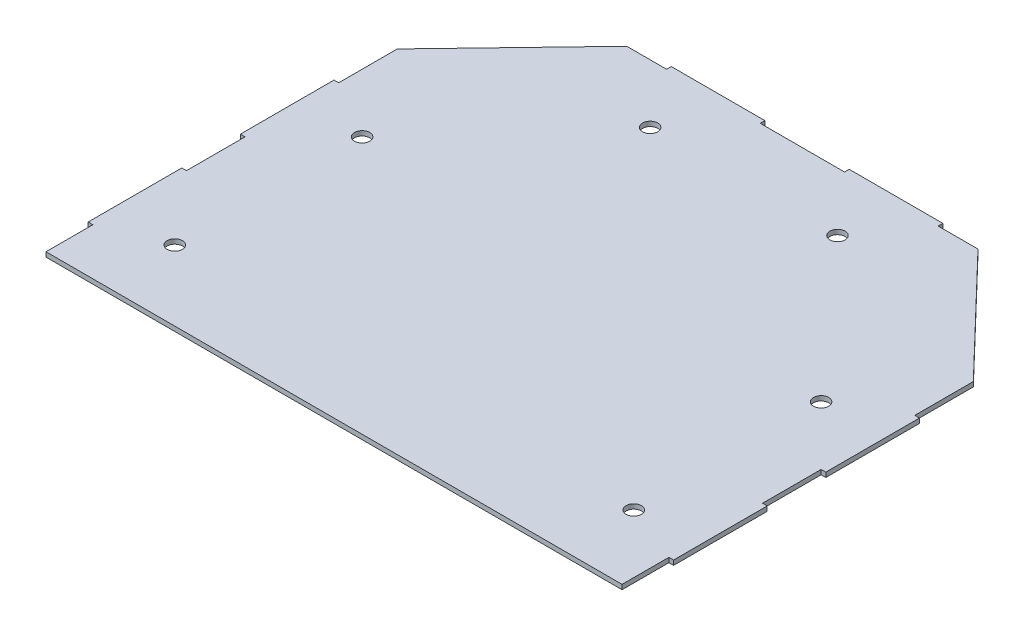
SolidWorks part; units mm, degrees
material "ABS PC"
ref_plane "Спереди" through (0, 0, 0) normal (0, 0, 1) x (1, 0, 0)
ref_plane "Сверху" through (0, 0, 0) normal (0, 1, 0) x (1, 0, 0)
ref_plane "Справа" through (0, 0, 0) normal (1, 0, 0) x (0, 0, -1)
sketch "Sketch1" plane through (0, 0, 0) normal (0, 1, 0) x (1, 0, 0)
  line L0 (-123, 0) -> (-123, 20)
  line L1 (-123, 150) -> (-75, 200)
  line L2 (-75, 200) -> (-58, 200)
  line L3 (0, 200) -> (0, 0) construction
  line L4 (123, 0) -> (-123, 0)
  line L5 (-123, 0) -> (-123.0387, -0.1129)
  line L6 (-123, 20) -> (-125, 20)
  line L7 (-125, 20) -> (-125, 60)
  line L8 (-125, 60) -> (-123, 60)
  line L9 (-123, 85) -> (-125, 85)
  line L10 (-125, 85) -> (-125, 125)
  line L11 (-125, 125) -> (-123, 125)
  line L12 (-123, 125) -> (-123, 150)
  line L13 (-123, 60) -> (-123, 85)
  line L14 (-58, 200) -> (-58, 202)
  line L15 (-58, 202) -> (-18, 202)
  line L16 (-18, 202) -> (-18, 200)
  line L17 (-18, 200) -> (18, 200)
  line L18 (18, 202) -> (18, 200)
  line L19 (58, 202) -> (18, 202)
  line L20 (58, 200) -> (58, 202)
  line L21 (123, 60) -> (123, 85)
  line L22 (123, 125) -> (123, 150)
  line L23 (125, 125) -> (123, 125)
  line L24 (125, 85) -> (125, 125)
  line L25 (123, 85) -> (125, 85)
  line L26 (125, 60) -> (123, 60)
  line L27 (125, 20) -> (125, 60)
  line L28 (123, 20) -> (125, 20)
  line L29 (123, 0) -> (123.0387, -0.1129)
  line L30 (75, 200) -> (58, 200)
  line L31 (123, 150) -> (75, 200)
  line L32 (123, 0) -> (123, 20)
  dimension "D1" = 123
  dimension "D2" = 200
  dimension "D3" = 50
  dimension "D4" = 75
  dimension "D5" = 40
  dimension "D6" = 180
  dimension "D7" = 115
  dimension "D8" = 2
  dimension "D9" = 65
extrude "Boss-Extrude1" add sketch "Sketch1" along normal blind 2 contours L3 L17 L16 L15 L14 L2 L1 L12 L11 L10 L9 L13 L8 L7 L6 L0 L4 | L17 L3 L4 L32 L28 L27 L26 L21 L25 L24 L23 L22 L31 L30 L20 L19 L18 region at (-59.5338, 0, -95.9255) region at (59.5338, 0, -95.9255)
sketch "Sketch2" plane through (0, 2, 0) normal (0, 1, 0) x (-1, 0, 0)
  line L0 (98, -110) -> (98, -30) construction
  line L1 (-98, -110) -> (-98, -30) construction
  line L2 (98, -110) -> (0, -110) construction
  line L3 (0, -110) -> (-98, -110) construction
  line L4 (-123, 0) -> (123, 0) construction
  line L5 (123, -125) -> (123, -150) construction
  line L6 (40, -175) -> (0, -175) construction
  line L7 (-40, -175) -> (0, -175) construction
  line L8 (18, -200) -> (-18, -200) construction
  circle A0 centre (98, -110) radius 3.25
  circle A1 centre (98, -30) radius 3.25
  circle A2 centre (-98, -30) radius 3.25
  circle A3 centre (-98, -110) radius 3.25
  circle A4 centre (40, -175) radius 3.25
  circle A5 centre (-40, -175) radius 3.25
  point P8 (0, -110)
  dimension "D1" = 6.5
  dimension "D2" = 25
  dimension "D3" = 110
  dimension "D4" = 80
  dimension "D5" = 25
  dimension "D6" = 40
extrude "Cut-Extrude1" cut sketch "Sketch2" against normal through all
